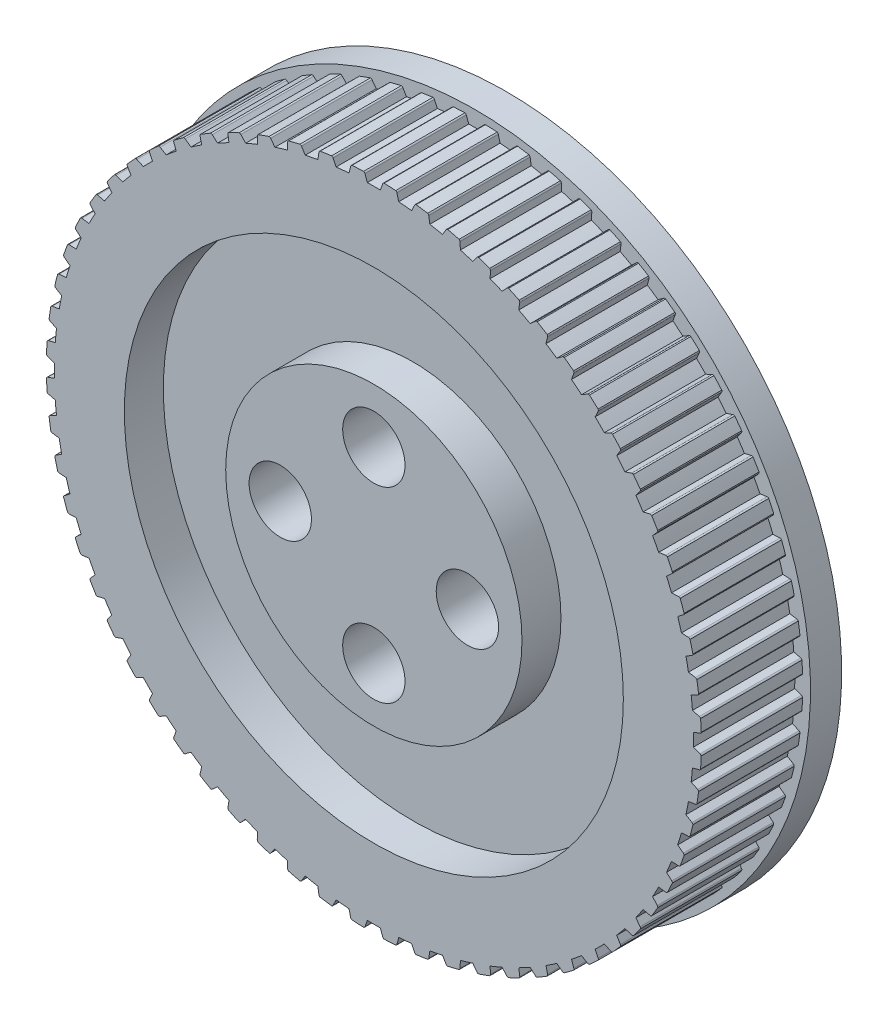
SolidWorks part; units mm, degrees
ref_plane "Plan de face" through (0, 0, 0) normal (0, 0, 1) x (1, 0, 0)
ref_plane "Plan de dessus" through (0, 0, 0) normal (0, 1, 0) x (1, 0, 0)
ref_plane "Plan de droite" through (0, 0, 0) normal (1, 0, 0) x (0, 0, -1)
sketch "Esquisse1" plane through (0, 0, 0) normal (0, 0, 1) x (1, 0, 0)
  line L0 (0, 0) -> (0, 11.7813) construction
  circle A0 centre (0, 0) radius 21
  dimension "D1" = 42
extrude "Boss.-Extru.1" add sketch "Esquisse1" along normal blind 6.5 contours A0
sketch "Esquisse2" plane through (0, 0, 6.5) normal (0, 0, 1) x (1, 0, 0)
  line L9 (0, 0) -> (0, 30.3265) construction
  line L11 (-0.415, 20.4875) -> (-0.5707, 20.9151)
  line L12 (-0.6917, 20.9915) -> (-1.016, 20.9754)
  line L14 (0.415, 20.4875) -> (0.5707, 20.9151)
  line L15 (0.6917, 20.9915) -> (1.016, 20.9754)
  line L22 (-0.415, 20.4875) -> (0.415, 20.4875) construction
  line L23 (-0.601, 20.9914) -> (-5.5088, 13.8157) construction
  line L24 (-1.016, 20.9754) -> (-1.016, 21.395)
  line L25 (-1.016, 21.395) -> (1.016, 21.395)
  line L26 (1.016, 21.395) -> (1.016, 20.9754)
  circle A0 centre (0, 0) radius 20.5
  circle A1 centre (0, 0) radius 21 construction
  arc A2 (-0.415, 20.4875) -> (0.415, 20.4875) centre (0, 0) cw
  arc A5 (-0.5707, 20.9151) -> (-0.6917, 20.9915) centre (-0.6805, 20.8752) ccw
  arc A6 (0.5707, 20.9151) -> (0.6917, 20.9915) centre (0.6805, 20.8752) cw
  point P11 (0, 20.4875)
  dimension "D1" = 41
  dimension "D8" = 52.785
  dimension "D9" = 0.4277
  dimension "D4" = 0.1169
  dimension "D2" = 70
  dimension "D3" = 0.186
  dimension "D5" = 0.83
  dimension "D6" = 0.3243
  dimension "D7" = 0.415
  dimension "D10" = 0.1431
  dimension "D11" = 0.3243
extrude "Enlèv. mat.-Extru.1" cut sketch "Esquisse2" against normal up to next contours L15 L26 L25 L24 L12 A5 L11 A2 L14 A6
pattern_circular "Répétition circulaire1" count 64 every 5.625 about axis through (0, 0, 6.5) along (0, 0, 1) of "Enlèv. mat.-Extru.1"
sketch "Esquisse4" plane through (0, 0, 0) normal (0, 0, -1) x (-1, 0, 0)
  circle A0 centre (0, 0) radius 21.5
  dimension "D1" = 43
extrude "Boss.-Extru.3" add sketch "Esquisse4" along normal blind 2
sketch "Esquisse6" plane through (0, 0, -2) normal (0, 0, -1) x (-1, 0, 0)
  circle A0 centre (0, 0) radius 16
  dimension "D1" = 32
extrude "Enlèv. mat.-Extru.3" cut sketch "Esquisse6" against normal blind 2.5
sketch "Esquisse7" plane through (0, 0, 0.5) normal (0, 0, -1) x (-1, 0, 0)
  line L0 (0, -12.1143) -> (0, 11.7114) construction
  line L1 (-12.3476, 0) -> (12.7442, 0) construction
  circle A0 centre (6, 0) radius 2
  circle A1 centre (0, -6) radius 2
  circle A2 centre (-6, 0) radius 2
  circle A3 centre (0, 6) radius 2
  dimension "D1" = 6
  dimension "D3" = 6
  dimension "D4" = 6
  dimension "D5" = 6
extrude "Enlèv. mat.-Extru.4" cut sketch "Esquisse7" against normal through all
sketch "Esquisse8" plane through (0, 0, 6.5) normal (0, 0, 1) x (1, 0, 0)
  circle A0 centre (0, 0) radius 9.5
  circle A1 centre (0, 0) radius 16
  dimension "D1" = 19
  dimension "D2" = 32
extrude "Enlèv. mat.-Extru.5" cut sketch "Esquisse8" against normal blind 2.5
